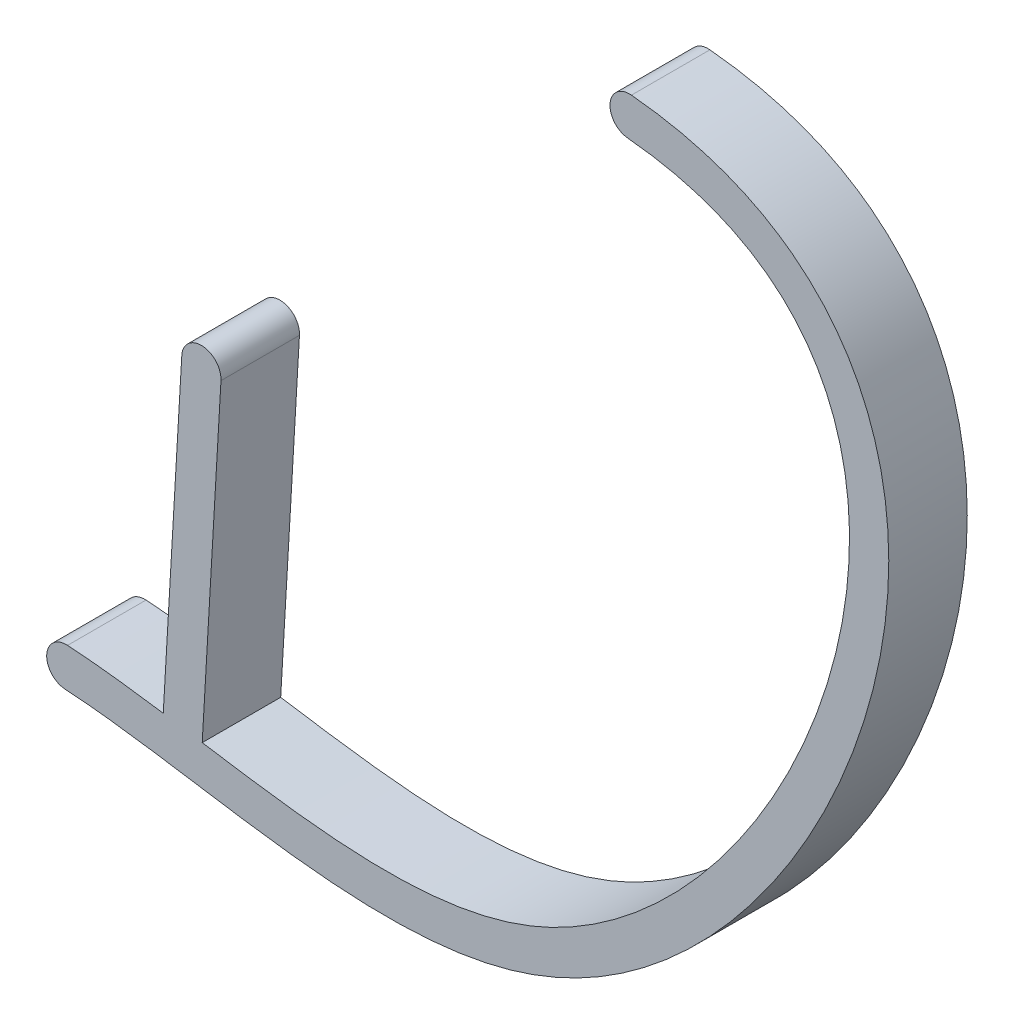
SolidWorks part; units mm, degrees
ref_plane "Front Plane" through (0, 0, 0) normal (0, 0, 1) x (1, 0, 0)
ref_plane "Top Plane" through (0, 0, 0) normal (0, 1, 0) x (1, 0, 0)
ref_plane "Right Plane" through (0, 0, 0) normal (1, 0, 0) x (0, 0, -1)
sketch "Sketch1" plane through (0, 0, 0) normal (0, 0, 1) x (1, 0, 0)
  arc A0 (-22.7744, -45.3184) -> (-25.944, -45.1342) centre (-24.3592, -45.2263) ccw
  arc A1 (-35.188, -70.0738) -> (-35.3865, -73.2426) centre (-35.2873, -71.6582) ccw
  arc A2 (10.4367, -8.7066) -> (10.1373, -11.8674) centre (10.287, -10.287) ccw
  spline S0 degree 3 poles (-27.4445, -70.9589) (-27.6676, -70.9258) (-29.0879, -70.7173) (-31.6916, -70.3664) (-34.0152, -70.1472) (-35.188, -70.0738) knots 0.931682 0.931682 0.931682 0.931682 0.9375 0.96875 1 1 1 1
  spline S3 degree 3 poles (10.1373, -11.8674) (10.5168, -11.9034) (11.2841, -11.9893) (12.7351, -12.205) (14.4476, -12.5591) (16.3283, -13.109) (18.6168, -13.9983) (21.0796, -15.382) (23.4576, -17.4254) (25.3152, -19.8201) (27.151, -23.4522) (28.2971, -28.7544) (27.9383, -35.9747) (25.9974, -43.5936) (22.6758, -51.1551) (18.1957, -58.2124) (12.7937, -64.3295) (7.7352, -68.2863) (3.4879, -70.5731) (-0.845, -72.2011) (-6.5168, -73.1252) (-13.629, -72.9561) (-19.6087, -72.1729) (-23.1598, -71.6188) (-24.2922, -71.4423) knots 0 0 0 0 0.007812 0.015625 0.03125 0.046875 0.0625 0.09375 0.125 0.15625 0.1875 0.25 0.3125 0.375 0.4375 0.5 0.5625 0.625 0.65625 0.6875 0.75 0.8125 0.875 0.904364 0.904364 0.904364 0.904364
  spline S5 degree 3 poles (10.4367, -8.7066) (10.8528, -8.746) (11.6923, -8.84) (13.2961, -9.0782) (15.2088, -9.4732) (17.344, -10.0968) (19.9847, -11.1217) (22.8982, -12.7534) (25.7718, -15.2194) (28.0206, -18.1203) (30.207, -22.4577) (31.5015, -28.5586) (31.0913, -36.4892) (29.0063, -44.6495) (25.4863, -52.6567) (20.751, -60.1193) (15.0013, -66.6311) (8.4383, -71.7946) (1.1855, -75.1129) (-6.347, -76.3106) (-13.9167, -76.124) (-20.1468, -75.304) (-25.0132, -74.5427) (-28.586, -73.9885) (-31.4782, -73.5987) (-33.7377, -73.3632) (-34.8335, -73.2772) (-35.3865, -73.2426) knots 0 0 0 0 0.007812 0.015625 0.03125 0.046875 0.0625 0.09375 0.125 0.15625 0.1875 0.25 0.3125 0.375 0.4375 0.5 0.5625 0.625 0.6875 0.75 0.8125 0.875 0.90625 0.9375 0.96875 0.984375 1 1 1 1
  spline S7 degree 3 poles (-24.2922, -71.4423) (-23.7863, -62.7343) (-23.2803, -54.0264) (-22.7744, -45.3184) knots 0.052231 0.052231 0.052231 0.052231 1 1 1 1
  spline S9 degree 3 poles (-27.4445, -70.9589) (-26.9443, -62.3507) (-26.4442, -53.7425) (-25.944, -45.1342) knots 0.063086 0.063086 0.063086 0.063086 1 1 1 1
extrude "Boss-Extrude1" add sketch "Sketch1" along normal blind 6.35 contours S9 A0 S7 S3 A2 S5 A1 S0
